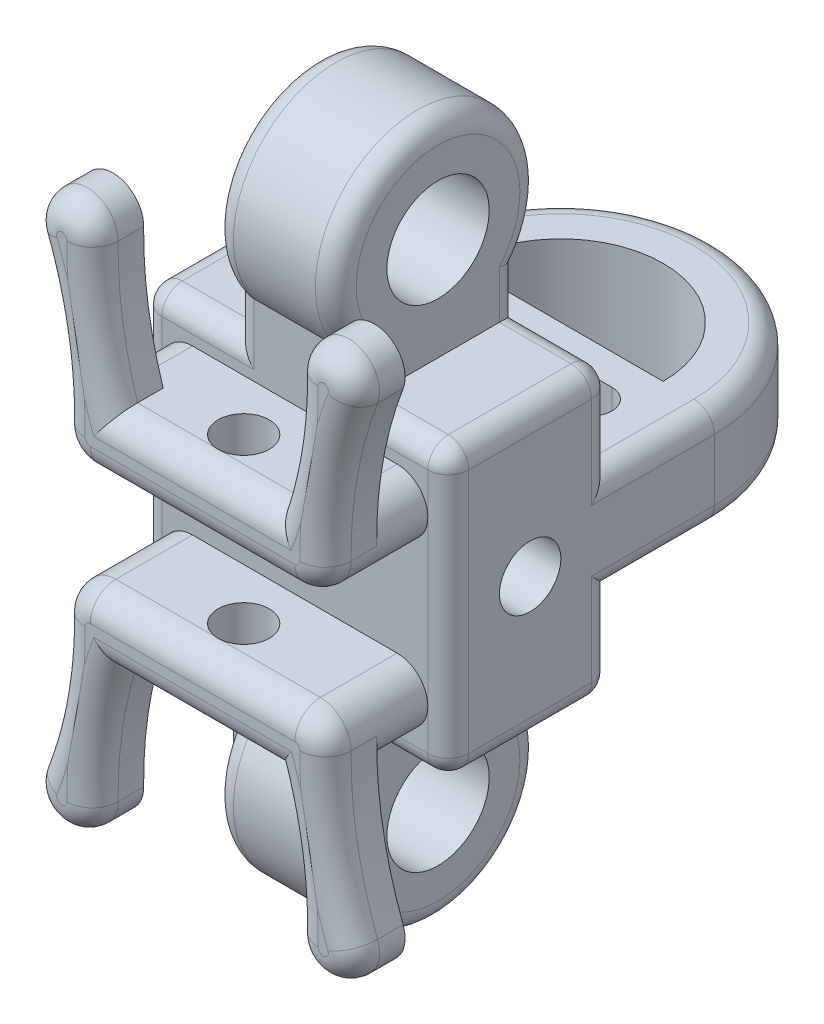
SolidWorks part; units mm, degrees
ref_plane "前视基准面" through (0, 0, 0) normal (0, 0, 1) x (1, 0, 0)
ref_plane "上视基准面" through (0, 0, 0) normal (0, 1, 0) x (1, 0, 0)
ref_plane "右视基准面" through (0, 0, 0) normal (1, 0, 0) x (0, 0, -1)
other "Configuration Table"
sketch "Sketch2" plane through (0, 0, 0) normal (1, 0, 0) x (0, 0, -1)
  line L1 (-4, -11) -> (4, -11)
  line L2 (-4, -11) -> (-4, 5)
  line L4 (4, -11) -> (4, 5)
  line L5 (-4, -11) -> (1.1387, 3.1314) construction
  line L6 (-1.1387, 3.1314) -> (4, -11) construction
  circle A0 centre (0, 8) radius 5
  circle A1 centre (0, 8) radius 2.5
  point P0 (0, 0)
  dimension "D1" = 10
  dimension "D2" = 5
  dimension "D3" = 16
  dimension "D4" = 8
  dimension "8" = 8
extrude "Boss-Extrude2" add sketch "Sketch2" along normal mid plane 15 contours A0 A1 | A0 L2 L1 L4 region at (0, -3.6877, 0) region at (0, 12.6093, 1.5364)
sketch "Sketch3" plane through (0, 0, 0) normal (0, 0, 1) x (1, 0, 0)
  line L0 (0, 13) -> (0, 5) construction
  line L1 (7.5, 13) -> (-7.5, 13) construction
  line L2 (7.5, 5) -> (-7.5, 5) construction
  line L3 (-3, 13) -> (3, 13)
  line L4 (3, 13) -> (3, 3)
  line L5 (3, 3) -> (-3, 3)
  line L6 (-3, 13) -> (-3, 3)
  line L7 (-3, 13) -> (-7.5, 13)
  line L8 (-7.5, 13) -> (-7.5, 3)
  line L9 (-7.5, -11) -> (-7.5, 5) construction
  line L10 (-7.5, 3) -> (-3, 3)
  line L11 (3, 3) -> (7.5, 3)
  line L12 (7.5, -11) -> (7.5, 5) construction
  line L13 (7.5, 3) -> (7.5, 13)
  line L14 (7.5, 13) -> (3, 13)
  dimension "D1" = 3
  dimension "D2" = 10
extrude "Cut-Extrude1" cut sketch "Sketch3" against normal mid plane 15 contours L13 L14 L4 L11 | L8 L10 L6 L7 region at (-5.25, 8, 0) region at (5.25, 8, 0)
ref_plane "Plane1" through (0, -4, 0) normal (0, -1, 0) x (-1, 0, 0)
mirror "Mirror1" about plane through (0, -4, 0) normal (0, -1, 0) of "Cut-Extrude1", "Boss-Extrude2"
sketch "Sketch5" plane through (-7.5, 0, 0) normal (-1, 0, 0) x (0, 0, 1)
  line L0 (4, -4) -> (-4, -4) construction
  line L1 (4, -11) -> (4, 3) construction
  line L2 (-4, -11) -> (-4, 3) construction
  line L3 (-4, -4) -> (0, -4) construction
  line L4 (0, -4) -> (0, 1) construction
  circle A0 centre (0, -4) radius 1.5
  dimension "D1" = 3
  dimension "D2" = 5
extrude "Cut-Extrude3" cut sketch "Sketch5" against normal through all
sketch "Sketch7" plane through (0, 0, -4) normal (0, 0, -1) x (-1, 0, 0)
  line L0 (-3, 3) -> (-3, -11) construction
  line L1 (-3, -11) -> (3, -11) construction
  line L2 (3, -11) -> (3, 3) construction
  line L3 (3, 3) -> (-3, 3) construction
  line L4 (-3, 3) -> (3, -11) construction
  line L5 (3, -11) -> (0, -4) construction
  line L7 (-7.5, -6.5) -> (7.5, -6.5)
  line L8 (-7.5, -6.5) -> (-7.5, -1.5)
  line L9 (-7.5, -1.5) -> (7.5, -1.5)
  line L10 (7.5, -6.5) -> (7.5, -1.5)
  line L11 (-7.5, -6.5) -> (7.5, -1.5) construction
  line L12 (-7.5, -1.5) -> (7.5, -6.5) construction
  dimension "D1" = 15
  dimension "D2" = 5
extrude "Boss-Extrude3" add sketch "Sketch7" along normal blind 5
sketch "Sketch8" plane through (0, -1.5, 0) normal (0, 1, 0) x (1, 0, 0)
  line L0 (-7.5, 9) -> (7.5, 9) construction
  line L1 (-7.5, 9) -> (7.5, 9)
  arc A0 (7.5, 9) -> (-7.5, 9) centre (0, 9) ccw
  arc A1 (5, 9) -> (-5, 9) centre (0, 9) ccw
  line M3 (7.5, 9) -> (-7.5, 9)
  dimension "D1" = 10
extrude "Boss-Extrude4" add sketch "Sketch8" against normal blind 5 contours A1 A0 M3 region at (0, -1.5, -16.3323)
sketch "Sketch9" plane through (0, -1.5, 0) normal (0, 1, 0) x (1, 0, 0)
  line L0 (0, 9) -> (0, 6.5) construction
  line L1 (-5, 9) -> (5, 9) construction
  line L2 (0, 6.5) -> (4, 6.5) construction
  line L3 (4, 6.5) -> (-4, 6.5) construction
  line L4 (4, 5.5) -> (-4, 5.5)
  line L5 (4, 7.5) -> (-4, 7.5)
  arc A0 (4, 5.5) -> (4, 7.5) centre (4, 6.5) ccw
  arc A1 (-4, 7.5) -> (-4, 5.5) centre (-4, 6.5) ccw
  point P5 (0, 6.5)
  dimension "D4" = 1
  dimension "D1" = 2.5
  dimension "D2" = 4
  dimension "D3" = 8
extrude "Cut-Extrude4" cut sketch "Sketch9" against normal blind 5
sketch "Sketch10" plane through (0, 0, 4) normal (0, 0, 1) x (1, 0, 0)
  line L0 (-3, 3) -> (3, -11) construction
  line L1 (3, -11) -> (-3, -11) construction
  line L2 (-3, -11) -> (0, -4) construction
  line L3 (0, -8) -> (0, 0) construction
  line L4 (0, 0) -> (5, 0) construction
  line L5 (5, 0) -> (-5, 0) construction
  line L6 (5, -1.5) -> (-5, -1.5)
  line L7 (5, 1.5) -> (-5, 1.5)
  line L8 (0, -4) -> (6.4228, -4) construction
  line L9 (-55, -4) -> (55, -4) construction
  line L10 (0, -8) -> (5, -8) construction
  line L11 (-3, 3) -> (0, -4) construction
  line L12 (-3, -11) -> (3, 3) construction
  line L13 (5, -8) -> (-5, -8) construction
  line L14 (5, -6.5) -> (-5, -6.5)
  line L15 (5, -9.5) -> (-5, -9.5)
  arc A0 (5, -1.5) -> (5, 1.5) centre (5, 0) ccw
  arc A1 (-5, 1.5) -> (-5, -1.5) centre (-5, 0) ccw
  arc A2 (5, -6.5) -> (5, -9.5) centre (5, -8) cw
  arc A3 (-5, -9.5) -> (-5, -6.5) centre (-5, -8) cw
  point P7 (0, 0)
  point P23 (0, -8)
  dimension "D3" = 1.5
  dimension "D1" = 5
  dimension "D2" = 10
extrude "Boss-Extrude5" add sketch "Sketch10" along normal blind 2.5
sketch "Sketch11" plane through (0, 0, 6.5) normal (0, 0, 1) x (1, 0, 0)
  line L0 (-6.5, -8) -> (6.5, -8) construction
  line L1 (6.5, -8) -> (0, -8) construction
  line L2 (-5, -8) -> (-6.3892, -15.8785) construction
  line L3 (-5, -8) -> (0, -8) construction
  line L4 (0, -8) -> (5, -8) construction
  line L5 (0, -8) -> (0, -7.6457) construction
  line L6 (5, -8) -> (6.3892, -15.8785) construction
  line L7 (-5, -6.5) -> (5, -6.5)
  line L8 (-5, -9.5) -> (5, -9.5)
  arc A0 (-5, -6.5) -> (-5, -9.5) centre (-5, -8) ccw construction
  arc A1 (5, -9.5) -> (5, -6.5) centre (5, -8) ccw construction
  circle A2 centre (-6.3892, -15.8785) radius 1.5
  circle A3 centre (6.3892, -15.8785) radius 1.5
  circle A4 centre (-5, -8) radius 1.5
  circle A5 centre (5, -8) radius 1.5
  arc A6 (-7.7921, -15.3477) -> (-6.4999, -8.0189) centre (-26.4983, -8.271) ccw
  arc A7 (-4.8893, -15.8596) -> (-3.597, -8.5308) centre (15.1091, -15.6075) cw
  arc A8 (4.8893, -15.8596) -> (3.597, -8.5308) centre (-15.1091, -15.6075) ccw
  arc A9 (7.7921, -15.3477) -> (6.4999, -8.0189) centre (26.4983, -8.271) cw
  point P12 (0, 0)
  point P35 (0, -6.8584)
  point P36 (0, 0)
  dimension "D1" = 3
  dimension "D4" = 3
  dimension "D5" = 20
  dimension "D2" = 100
  dimension "D3" = 8
  dimension "D6" = 10
extrude "Boss-Extrude6" add sketch "Sketch11" along normal blind 2.5 contours L8 A8 A5 L7 A4 A7 | A4 | A2 A7 L8 A4 A6 | A2 | L8 A7 A4 | A5 | A8 L8 A5 | A3 A9 A5 L8 A8 | A3 L7 | A5 region at (0, -7.9767, 6.5) region at (-5, -8, 6.5) region at (5, -8, 6.5) region at (-5.7199, -11.9811, 6.5) region at (4.0956, -9.2916, 6.5) region at (-4.0956, -9.2916, 6.5) region at (-6.3892, -15.8785, 6.5) region at (5.7199, -11.9811, 6.5) region at (6.3892, -15.8785, 6.5)
mirror "Mirror2" about plane through (0, -4, 0) normal (0, -1, 0) of "Boss-Extrude6"
fillet "Fillet1" radius 1 34 edges at (7.5, -6.5, -6.5) (-7.5, -6.5, -6.5) (7.5, -1.5, -6.5) (0, -1.5, -16.5) (5.25, 3, 4) (-5.25, 3, 4) (-7.5, 3, 0) (-5.25, 3, -4) (5.25, 3, -4) (7.5, 3, 0) (7.5, 0.75, -4) (7.5, -4, 4) (5.25, -11, 4) (7.5, -11, 0) (5.25, -11, -4) (-5.25, -11, 4) (-5.25, -11, -4) (-7.5, -11, 0) (-7.5, -8.75, -4) (0, -6.5, -16.5) (-7.5, -1.5, -6.5) (-7.5, 0.75, -4) (-7.5, -4, 4) (3, 13, 0) (-3, 13, 0) (3, -12, -4) (3, -21, 0) (-3, -12, -4) (-3, -21, 0) (-3, 4, 4) (3, -12, 4) (3, 4, 4) (3, 4, -4) (7.5, -8.75, -4)
sketch "Sketch12" plane through (0, 1.5, 0) normal (0, 1, 0) x (1, 0, 0)
  line L0 (0, -9) -> (0, -4) construction
  line L1 (-3.9355, -9) -> (3.9355, -9) construction
  line L2 (5, -4) -> (-5, -4) construction
  line L3 (0, -4) -> (0, -6.5) construction
  circle A0 centre (0, -6.5) radius 1.25
  dimension "D1" = 2.5
extrude "Cut-Extrude5" cut sketch "Sketch12" against normal through all
fillet "Fillet3" radius 1.25 20 edges at (6.8021, -11.7439, 9) (6.6497, -17.3557, 9) (4.6697, -12.6412, 9) (0, -9.5, 9) (-4.6697, -12.6412, 9) (-6.6497, -17.3557, 9) (-6.8021, -11.7439, 9) (-6.0673, -6.946, 9) (0, -6.5, 9) (6.0673, -6.946, 9) (-6.0673, -1.054, 9) (-6.8021, 3.7439, 9) (-6.6497, 9.3557, 9) (-4.6697, 4.6412, 9) (0, 1.5, 9) (4.6697, 4.6412, 9) (6.6497, 9.3557, 9) (6.8021, 3.7439, 9) (6.0673, -1.054, 9) (0, -1.5, 9)
